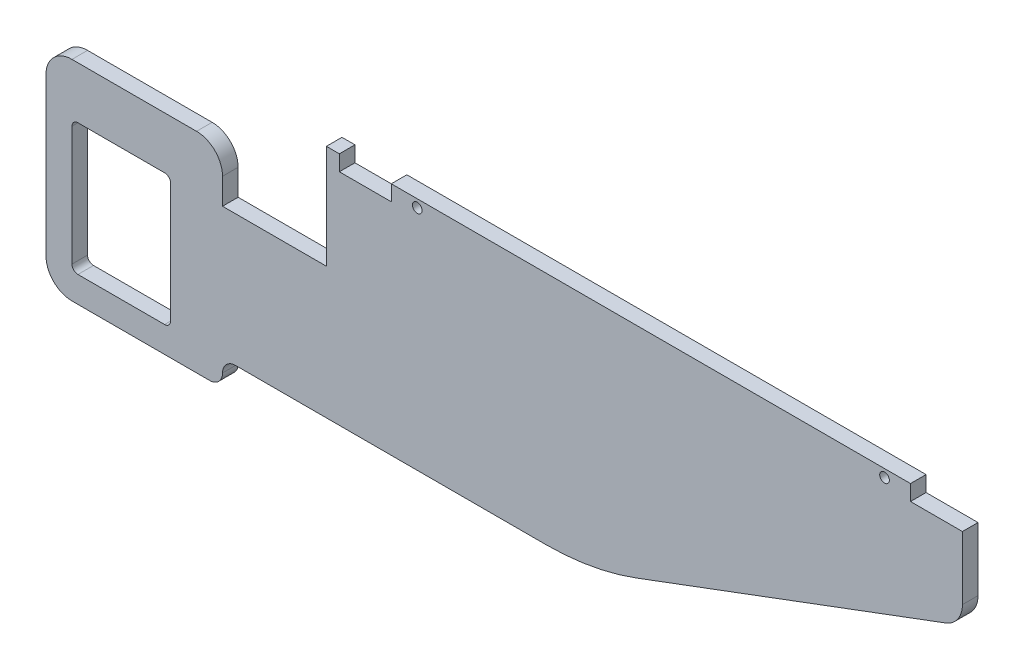
SolidWorks part; units mm, degrees
ref_plane "Front" through (0, 0, 0) normal (0, 0, 1) x (1, 0, 0)
ref_plane "Top" through (0, 0, 0) normal (0, 1, 0) x (1, 0, 0)
ref_plane "Right" through (0, 0, 0) normal (1, 0, 0) x (0, 0, -1)
sketch "Sketch1" plane through (0, 0, 0) normal (0, 0, 1) x (1, 0, 0)
  line L0 (58, 0) -> (58, -10)
  line L1 (2.3, 50.6) -> (35.7, 50.6)
  line L2 (0, 48.3) -> (0, 2.3)
  line L3 (2.3, 0) -> (35.7, 0)
  line L4 (200.6, 0) -> (343, 53.2686)
  line L5 (98, 90.6) -> (103, 90.6)
  line L6 (38, 48.3) -> (38, 2.3)
  line L7 (58, 0) -> (200.6, 0)
  line L8 (343, 84.6) -> (343, 53.2686)
  line L9 (-10, 70.6) -> (58, 70.6)
  line L10 (-10, 70.6) -> (-10, -10)
  line L11 (-10, -10) -> (58, -10)
  line L12 (58, 70.6) -> (58, 58.4409)
  line L13 (123, 90.6) -> (323, 90.6)
  line L14 (133, 87.6) -> (123, 87.6) construction
  line L16 (343, 84.6) -> (323, 84.6)
  line L17 (323, 90.6) -> (323, 84.6)
  line L19 (103, 90.6) -> (103, 84.6)
  line L20 (103, 84.6) -> (123, 84.6)
  line L21 (123, 90.6) -> (123, 84.6)
  line L22 (58, 58.4409) -> (58, 50.6)
  line L23 (58, 50.6) -> (98, 50.6)
  line L24 (98, 90.6) -> (98, 50.6)
  circle A0 centre (313, 87.6) radius 1.86
  circle A1 centre (133, 87.6) radius 1.86
  arc A2 (2.3, 50.6) -> (0, 48.3) centre (2.3, 48.3) ccw
  arc A3 (0, 2.3) -> (2.3, 0) centre (2.3, 2.3) ccw
  arc A4 (38, 2.3) -> (35.7, 0) centre (35.7, 2.3) cw
  arc A5 (35.7, 50.6) -> (38, 48.3) centre (35.7, 48.3) cw
  point P30 (0, 50.6)
  point P33 (0, 0)
  point P36 (38, 0)
  point P39 (38, 50.6)
  dimension "D12" = 3.72
  dimension "D17" = 2.3
  dimension "D1" = 38
  dimension "D2" = 50.6
  dimension "D3" = 20
  dimension "D4" = 10
  dimension "D5" = 20
  dimension "D6" = 10
  dimension "D7" = 20
  dimension "D8" = 20
  dimension "D9" = 200
  dimension "D10" = 6
  dimension "D11" = 305
  dimension "D13" = 10
  dimension "D14" = 10
  dimension "D15" = 40
  dimension "D16" = 40
extrude "Extrude1" add sketch "Sketch1" along normal blind 6
fillet "Fillet1" radius 10 4 edges at (-10, 70.6, 3) (-10, -10, 3) (58, 70.6, 3) (343, 53.2686, 3)
fillet "Fillet2" radius 5 2 edges at (58, 0, 3) (58, -10, 3)
fillet "Fillet4" radius 100 1 edges at (200.6, 0, 3)
